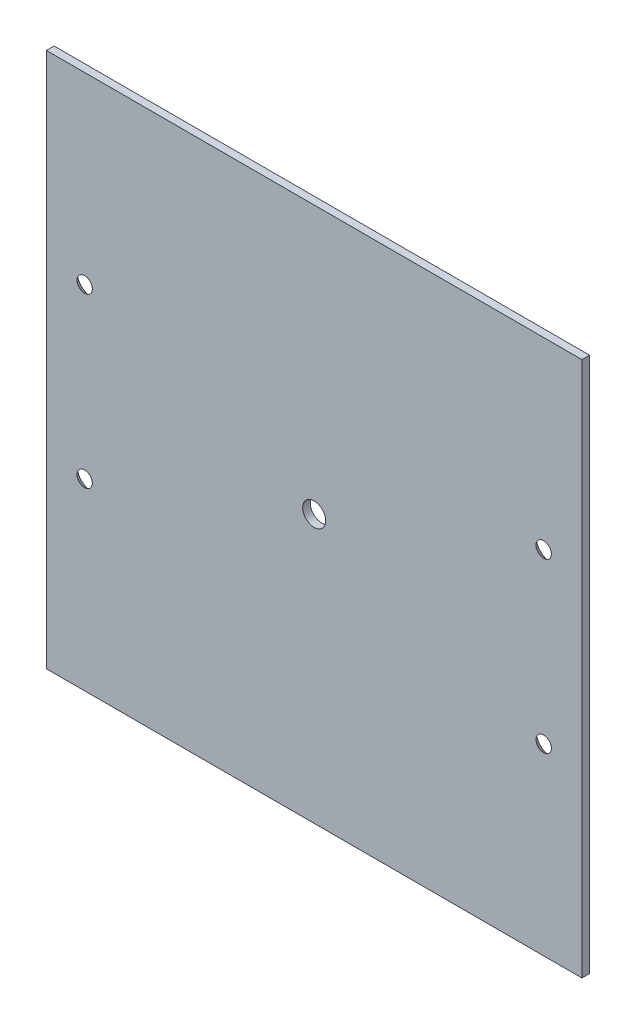
SolidWorks part; units mm, degrees
material "Ceramic Porcelain"
ref_plane "Front Plane" through (0, 0, 0) normal (0, 0, 1) x (1, 0, 0)
ref_plane "Top Plane" through (0, 0, 0) normal (0, 1, 0) x (1, 0, 0)
ref_plane "Right Plane" through (0, 0, 0) normal (1, 0, 0) x (0, 0, -1)
sketch "Sketch1" plane through (0, 0, 0) normal (0, 0, 1) x (1, 0, 0)
  line L0 (140, 70) -> (0, 70) construction
  line L1 (0, 0) -> (140, 0)
  line L2 (0, 0) -> (0, 140)
  line L3 (0, 140) -> (140, 140)
  line L4 (140, 0) -> (140, 140)
  dimension "D1" = 140
  dimension "D5" = 140
extrude "Boss-Extrude1" add sketch "Sketch1" along normal blind 2
hole_wizard "CSK for M3 Flat Head Machine Screw1" positions "Sketch6" profile "Sketch5" countersink size "M3" standard "Ansi Metric" end condition through all
sketch "Sketch6" plane through (0, 0, 0) normal (0, 0, -1) x (-1, 0, 0)
  line L0 (6.0733, 70) -> (-132.5, 70) construction
  line L5 (-130, 92) -> (-130, 48) construction
  line L9 (-70, 140) -> (-70, 0) construction
  line L10 (-140, 140) -> (0, 140) construction
  line L11 (0, 0) -> (-140, 0) construction
  line L13 (-10, 92) -> (-10, 48) construction
  line L14 (-146.0733, 70) -> (-7.5, 70) construction
  point P20 (-130, 92)
  point P22 (-130, 48)
  point P48 (-10, 92)
  point P50 (-10, 48)
  dimension "D1" = 60
  dimension "D3" = 22
  dimension "D4" = 44
sketch "Sketch5" plane through (130, 92, 0) normal (1, 0, 0) x (0, 1, 0)
  line L0 (0, 0) -> (0, 2)
  line L1 (0, 2) -> (1.5, 2)
  line L2 (1.5, 2) -> (1.5, 2.5)
  line L3 (1.5, 2.5) -> (4, 0)
  line L5 (4, 0) -> (0, 0)
  line L6 (-1.5, 2.5) -> (-4, 0) construction
  line L11 (0, -6.35) -> (0, 107.95) construction
  dimension "Thru Hole Dia." = 3
  dimension "Thru Hole Depth" = 2
  dimension "Near C'Sink Dia." = 8
  dimension "Near C'Sink Angle" = 90
sketch "Sketch7" plane through (0, 0, 0) normal (0, 0, -1) x (-1, 0, 0)
  line L0 (-70, 140) -> (-70, 0) construction
  line L1 (-140, 140) -> (0, 140) construction
  line L2 (0, 0) -> (-140, 0) construction
  line L3 (-61.8, 132) -> (-78.2, 132) construction
  circle A0 centre (-78.2, 132) radius 1.5
  circle A1 centre (-61.8, 132) radius 1.5
  dimension "D2" = 3
  dimension "D3" = 8.2
  dimension "D1" = 8.2
  dimension "D4" = 8
extrude "Cut-Extrude1" [suppressed] cut sketch "Sketch7" against normal through all
sketch "Sketch8" plane through (0, 0, 0) normal (0, 0, -1) x (-1, 0, 0)
  line L0 (-140, 70) -> (0, 70) construction
  line L1 (-140, 0) -> (-140, 140) construction
  line L2 (0, 140) -> (0, 0) construction
  circle A0 centre (-70, 70) radius 3
  dimension "D1" = 6
extrude "Cut-Extrude2" cut sketch "Sketch8" against normal through all
